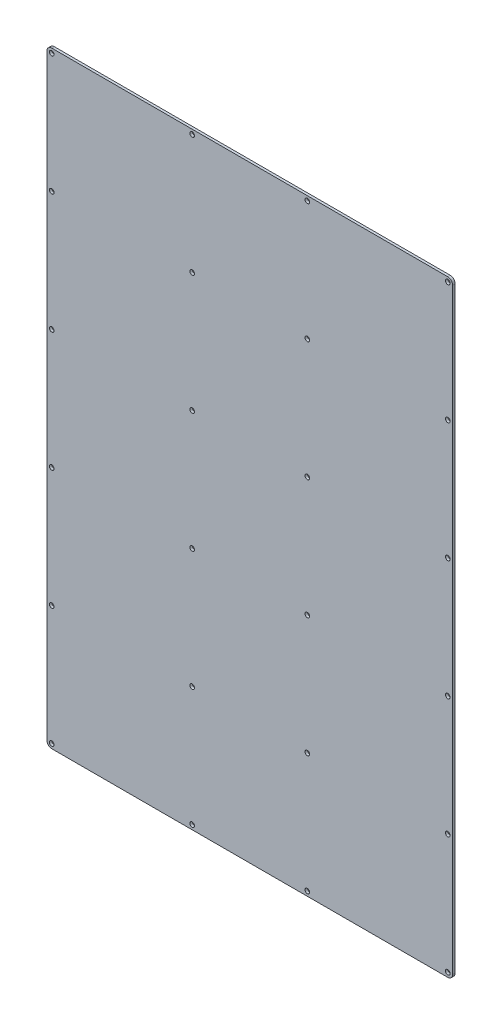
SolidWorks part; units mm, degrees
ref_plane "Front Plane" through (0, 0, 0) normal (0, 0, 1) x (1, 0, 0)
ref_plane "Top Plane" through (0, 0, 0) normal (0, 1, 0) x (1, 0, 0)
ref_plane "Right Plane" through (0, 0, 0) normal (1, 0, 0) x (0, 0, -1)
sketch "Sketch1" plane through (0, 0, 0) normal (0, 0, 1) x (1, 0, 0)
  line L1 (0, 0) -> (256.54, 0)
  line L2 (0, 0) -> (0, 383.54)
  line L3 (0, 383.54) -> (256.54, 383.54)
  line L4 (256.54, 0) -> (256.54, 383.54)
  dimension "D1" = 383.54
  dimension "D2" = 256.54
extrude "Boss-Extrude1" add sketch "Sketch1" along normal blind 1.5875
sketch "Sketch2" plane through (0, 0, 1.5875) normal (0, 0, 1) x (1, 0, 0)
  line L0 (256.54, 383.54) -> (0, 383.54) construction
  line L1 (-0.3175, 383.8575) -> (256.8575, 383.8575) construction
  line L2 (-0.3175, 383.8575) -> (-0.3175, -0.3175) construction
  line L4 (256.8575, 383.8575) -> (256.8575, -0.3175) construction
  line L5 (0, 383.54) -> (0, 0) construction
  line L6 (-0.3175, 380.6825) -> (256.8575, 380.6825) construction
  circle A0 centre (3.0861, 380.6825) radius 1.4732
  circle A1 centre (91.8845, 380.6825) radius 1.4732
  circle A2 centre (164.6555, 380.6825) radius 1.4732
  circle A3 centre (253.4539, 380.6825) radius 1.4732
  dimension "D2" = 384.175
  dimension "D6" = 2.9464
  dimension "D1" = 257.175
  dimension "D3" = 0.3175
  dimension "D4" = 0.3175
  dimension "D5" = 3.175
  dimension "D7" = 3.4036
  dimension "D8" = 88.7984
  dimension "D9" = 3.4036
  dimension "D10" = 88.7984
extrude "Cut-Extrude1" cut sketch "Sketch2" against normal through all
pattern_linear "LPattern1" count 6 spacing 75.565 along (0, -1, 0) of "Cut-Extrude1"
fillet "Fillet1" radius 3.175 4 edges at (256.54, 0, 0.7937) (0, 0, 0.7937) (256.54, 383.54, 0.7937) (0, 383.54, 0.7937)
